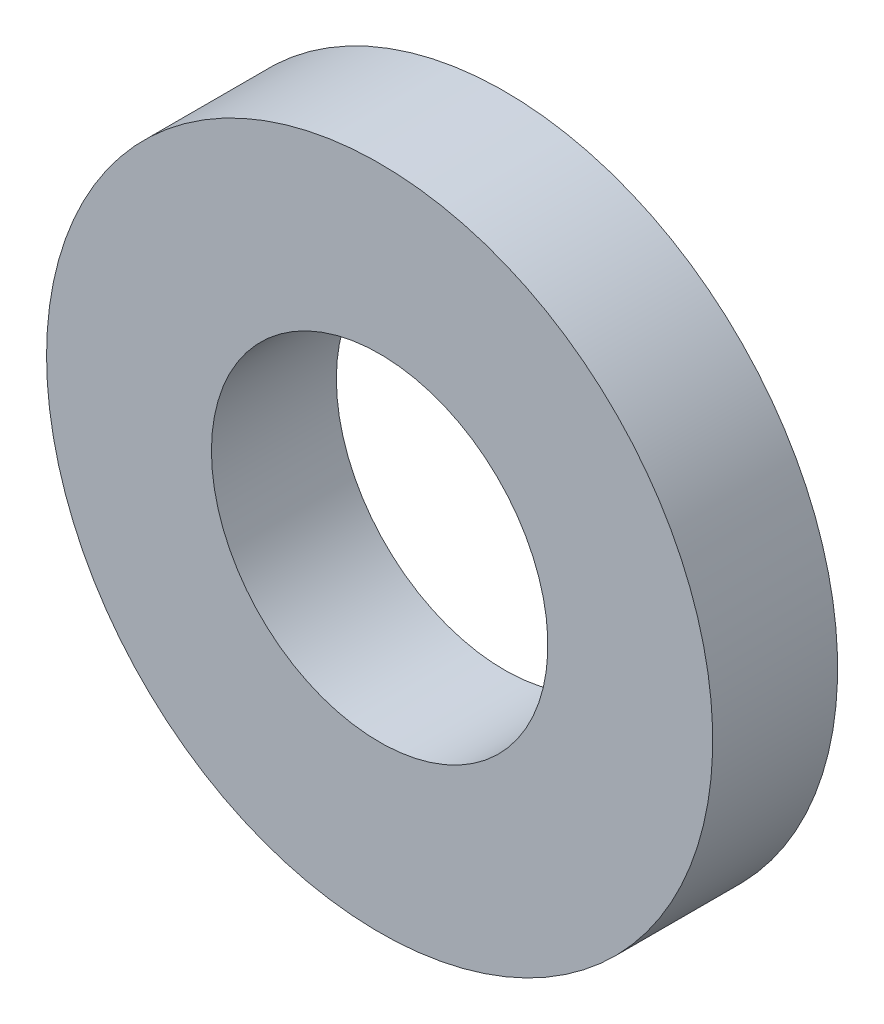
SolidWorks part; units mm, degrees
ref_plane "Front Plane" through (0, 0, 0) normal (0, 0, 1) x (1, 0, 0)
ref_plane "Top Plane" through (0, 0, 0) normal (0, 1, 0) x (1, 0, 0)
ref_plane "Right Plane" through (0, 0, 0) normal (1, 0, 0) x (0, 0, -1)
sketch "Sketch1" plane through (0, 0, 0) normal (0, 0, 1) x (1, 0, 0)
  circle A0 centre (0, 0) radius 12.7
  circle A1 centre (0, 0) radius 6.4135
  dimension "OD" = 25.4
  dimension "ID" = 12.827
extrude "Extrude1" add sketch "Sketch1" along normal mid plane 4.7625
sketch "Sketch2" plane through (0, 0, 0) normal (1, 0, 0) x (0, 0, -1)
  line L0 (-2.3812, -6.4135) -> (2.3812, -6.4135) construction
  line L3 (2.3812, 6.4135) -> (-2.3812, 6.4135) construction
  line L5 (-2.3812, -6.4135) -> (2.3812, -6.4135)
  line L6 (2.3812, 6.4135) -> (-2.3812, 6.4135)
sketch "Sketch4" plane through (0, 0, 2.3813) normal (0, 0, 1) x (1, 0, 0)
  line L0 (0, 0) -> (-4.535, 4.535)
  line L1 (0, -55) -> (0, 55) construction
  circle A0 centre (0, 0) radius 6.4135 construction
  dimension "D1" = 45
